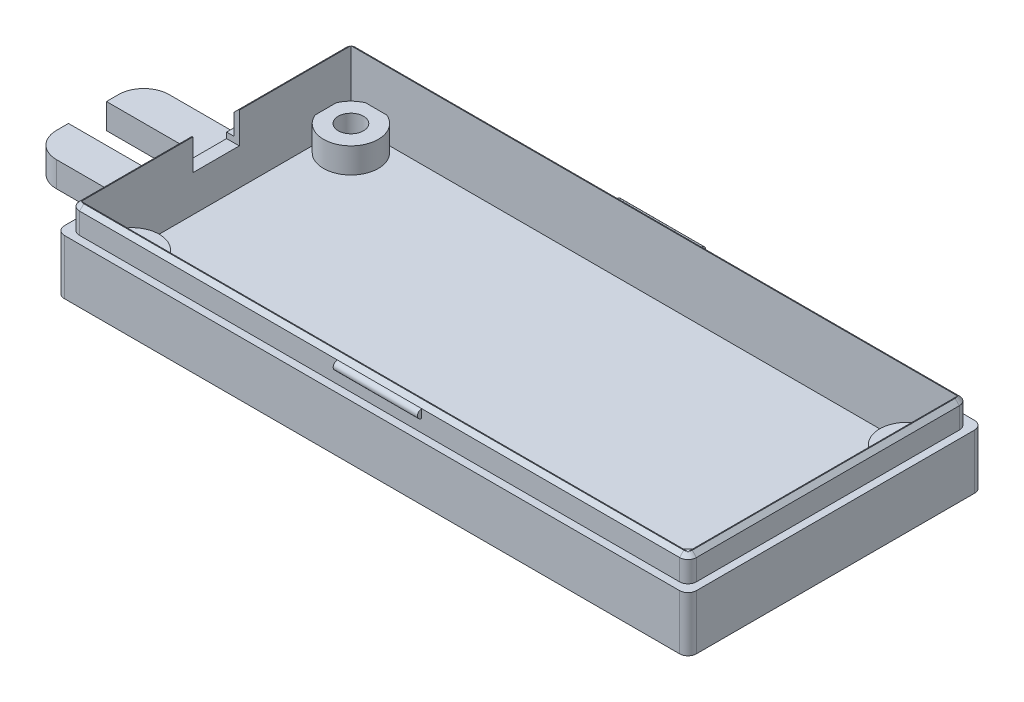
SolidWorks part; units mm, degrees
material "Настроенная пользователем пластмасса"
ref_plane "Спереди" through (0, 0, 0) normal (0, 0, 1) x (1, 0, 0)
ref_plane "Сверху" through (0, 0, 0) normal (0, 1, 0) x (1, 0, 0)
ref_plane "Справа" through (0, 0, 0) normal (1, 0, 0) x (0, 0, -1)
sketch "Эскиз5" plane through (0, 0, 0) normal (0, 1, 0) x (1, 0, 0)
  line L0 (-54.0987, 0) -> (61.0372, 0) construction
  line L1 (0, 31.2775) -> (0, -34.8552) construction
  line L3 (-33, 13) -> (33, 13) construction
  line L4 (-33, 13) -> (-33, -13) construction
  line L5 (-33, -13) -> (33, -13) construction
  line L6 (33, 13) -> (33, -13) construction
  line L7 (-33, 13) -> (33, -13) construction
  line L8 (-33, -13) -> (33, 13) construction
  line L9 (35, -15) -> (-35, -15)
  line L10 (35, -15) -> (35, 15)
  line L11 (35, 15) -> (-35, 15)
  line L12 (-35, -15) -> (-35, 15)
  line L13 (35, -15) -> (-35, 15) construction
  line L14 (35, 15) -> (-35, -15) construction
  point P5 (0, 0)
  point P10 (0, 0)
  dimension "D1" = 66
  dimension "D2" = 26
  dimension "D3" = 70
  dimension "D4" = 30
sketch "Эскиз6" plane through (0, 0, 0) normal (0, 1, 0) x (1, 0, 0)
  line L12 (-35, -15) -> (-35, 15) construction
  line L13 (-36, 16) -> (36, 16)
  line L14 (-36, 16) -> (-36, -16)
  line L15 (-36, -16) -> (36, -16)
  line L16 (36, 16) -> (36, -16)
  line L17 (-36, 16) -> (36, -16) construction
  line L18 (-36, -16) -> (36, 16) construction
  line L19 (-37.5, 17.5) -> (37.5, 17.5)
  line L20 (-37.5, 17.5) -> (-37.5, -17.5)
  line L21 (-37.5, -17.5) -> (37.5, -17.5)
  line L22 (37.5, 17.5) -> (37.5, -17.5)
  line L23 (-37.5, 17.5) -> (37.5, -17.5) construction
  line L24 (-37.5, -17.5) -> (37.5, 17.5) construction
  line L25 (35, 15) -> (-35, 15) construction
  point P0 (0, 0)
  point P5 (0, 0)
  dimension "D1" = 35
  dimension "D3" = 1.5
  dimension "D4" = 1.5
  dimension "D5" = 1
  dimension "D6" = 1
  dimension "D2" = 75
extrude "Бобышка-Вытянуть2" add sketch "Эскиз6" along normal blind 5
sketch "Эскиз7" plane through (0, 0, 0) normal (0, -1, 0) x (1, 0, 0)
  line L1 (-37.5, 17.5) -> (37.5, 17.5)
  line L2 (-37.5, 17.5) -> (-37.5, -17.5)
  line L3 (-37.5, -17.5) -> (37.5, -17.5)
  line L4 (37.5, 17.5) -> (37.5, -17.5)
extrude "Бобышка-Вытянуть3" add sketch "Эскиз7" along normal blind 1.5
fillet "Скругление2" radius 1 4 edges at (-37.5, 1.75, -17.5) (37.5, 1.75, -17.5) (37.5, 1.75, 17.5) (-37.5, 1.75, 17.5)
sketch "Эскиз8" plane through (0, 0, 0) normal (0, 1, 0) x (1, 0, 0)
  circle A0 centre (-33, 13) radius 3.25
  circle A1 centre (-33, 13) radius 1.5
  circle A2 centre (-33, -13) radius 1.5
  circle A3 centre (-33, -13) radius 3.25
  circle A4 centre (33, 13) radius 1.5
  circle A5 centre (33, 13) radius 3.25
  circle A6 centre (33, -13) radius 1.5
  circle A7 centre (33, -13) radius 3.25
extrude "Бобышка-Вытянуть4" add sketch "Эскиз8" along normal blind 3
sketch "Эскиз9" plane through (0, -1.5, 0) normal (0, -1, 0) x (1, 0, 0)
  line L0 (-36.2643, -6.6911) -> (-36.2643, 0)
  line L2 (-36.2643, 0) -> (-36.2665, 6.6824)
  line L3 (-36.2665, 6.6824) -> (-48.2643, 6.6824)
  line L4 (-51.2643, 3.6824) -> (-51.2643, 2.2505)
  line L5 (-48.2643, -6.6911) -> (-36.2643, -6.6911)
  line L6 (-51.2643, -3.6911) -> (-51.2643, -2.2592)
  line L7 (-51.2643, -2.2592) -> (-41.9057, -2.2592)
  line L9 (-51.2643, 2.2505) -> (-41.9057, 2.2505)
  line L10 (-39.9057, -0.2592) -> (-39.9057, 0.2505)
  line L11 (-54.0987, 0) -> (61.0372, 0) construction
  arc A0 (-51.2643, 3.6824) -> (-48.2643, 6.6824) centre (-48.2643, 3.6824) cw
  arc A1 (-51.2643, -3.6911) -> (-48.2643, -6.6911) centre (-48.2643, -3.6911) ccw
  arc A2 (-39.9057, 0.2505) -> (-41.9057, 2.2505) centre (-41.9057, 0.2505) ccw
  arc A3 (-39.9057, -0.2592) -> (-41.9057, -2.2592) centre (-41.9057, -0.2592) cw
  point P11 (-51.2643, 2.9664)
  dimension "D1" = 3
  dimension "D2" = 2
  dimension "D3" = 4.5096
  dimension "D4" = 15
extrude "Бобышка-Вытянуть5" add sketch "Эскиз9" against normal blind 3 separate body
sketch "Эскиз10" plane through (0, 5, 0) normal (0, 1, 0) x (1, 0, 0)
  line L1 (-36, 16) -> (36, 16)
  line L2 (-36, 16) -> (-36, -16)
  line L3 (-36, -16) -> (36, -16)
  line L4 (36, 16) -> (36, -16)
  line L5 (-36.6, 16.6) -> (36.6, 16.6)
  line L6 (-36.6, 16.6) -> (-36.6, -16.6)
  line L7 (-36.6, -16.6) -> (36.6, -16.6)
  line L8 (36.6, 16.6) -> (36.6, -16.6)
  dimension "D1" = 0.6
  dimension "D2" = 0.6
  dimension "D3" = 0.6
  dimension "D4" = 0.6
extrude "Бобышка-Вытянуть6" add sketch "Эскиз10" along normal blind 3
fillet "Скругление5" radius 1 4 edges at (36.6, 6.5, 16.6) (36.6, 6.5, -16.6) (-36.6, 6.5, 16.6) (-36.6, 6.5, -16.6)
sketch "Эскиз11" plane through (0, 0, 0) normal (1, 0, 0) x (0, 0, -1)
  line L0 (0, 0) -> (0, 1.5744) construction
  line L1 (2.75, 11.6925) -> (2.75, 4.3244)
  line L2 (2.75, 11.6925) -> (-2.75, 11.6925)
  line L3 (-2.75, 11.6925) -> (-2.75, 4.3244)
  line L4 (0, 11.6925) -> (0, 13.1716) construction
  line L5 (-2.75, 4.3244) -> (2.75, 4.3244)
  point P9 (0, 11.6925)
  dimension "D1" = 5.5
extrude "Вырез-Вытянуть1" cut sketch "Эскиз11" against normal blind 60
sketch "Эскиз12" plane through (0, 0, 0) normal (1, 0, 0) x (0, 0, -1)
  line L0 (0, 0) -> (0, 11.2034) construction
  line L2 (-16.6, 5) -> (-16.6, 8) construction
  line L3 (-16.5, 5) -> (-17.5, 5) construction
  circle A0 centre (-16.6, 7) radius 0.5
  circle A1 centre (16.6, 7) radius 0.5
  dimension "D2" = 1
  dimension "D1" = 2
extrude "Бобышка-Вытянуть7" add sketch "Эскиз12" along normal blind 5 and the other way blind 5
chamfer "Фаска1" distance 0.5 angle 45 9 edges at (36.6, 8, 0) (0, 8, -16.6) (-36.6, 8, -9.175) (-36.6, 8, 9.175) (-36.3071, 8, -16.3071) (36.3071, 8, -16.3071) (-36.3071, 8, 16.3071) (36.3071, 8, 16.3071) (0, 8, 16.6)
equation "\"MountWith\"= 67"
equation "\"MountDepth\"= 26"
equation "\"IntGap\"= 1"
equation "\"WallThickness\"= 1.5"
equation "\"MountHole\"= 3"
equation "\"PCBWidth\"= 70"
equation "\"PCBDepth\"= 30"
equation "\"ExtDepth\"= \"PCBDepth\" + \"IntGap\" * 2 + \"WallThickness\" * 2"
equation "\"ExtWidth\"= \"PCBWidth\" + \"IntGap\" * 2 + \"WallThickness\" * 2"
equation "\"D1@Эскиз6\"=\"ExtDepth\""
equation "\"MountLugHeight\"= 4"
equation "\"MountLugDiam\"= \"MountHole\" * 2.5"
